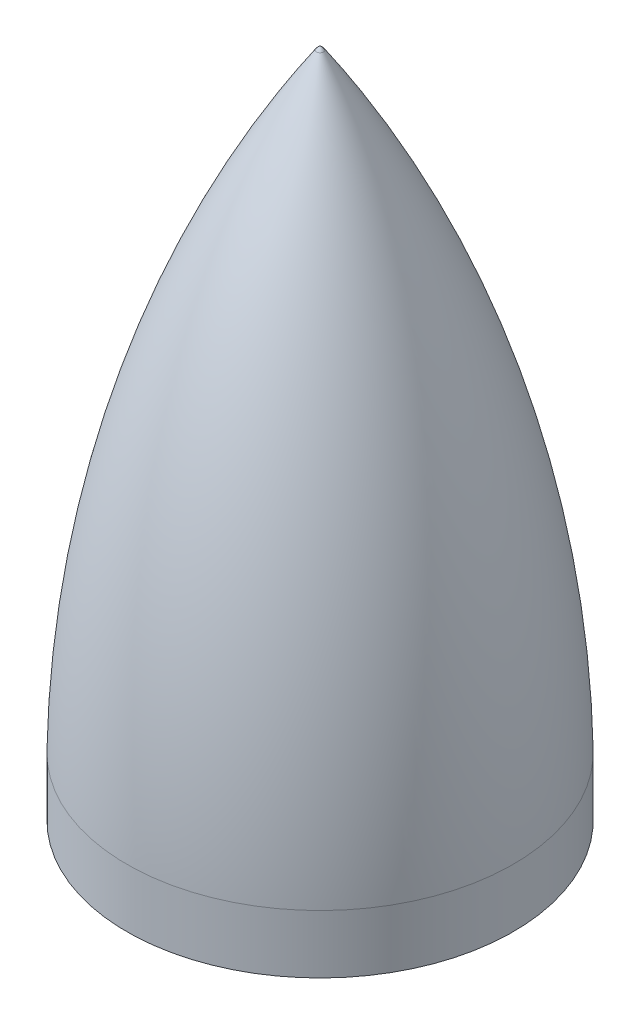
SolidWorks part; units mm, degrees
ref_plane "Спереди" through (0, 0, 0) normal (0, 0, 1) x (1, 0, 0)
ref_plane "Сверху" through (0, 0, 0) normal (0, 1, 0) x (1, 0, 0)
ref_plane "Справа" through (0, 0, 0) normal (1, 0, 0) x (0, 0, -1)
other "Configuration Table"
sketch "Эскиз1" plane through (0, 0, 0) normal (0, 0, 1) x (1, 0, 0)
  line L0 (0, 0) -> (0, 76824.2673) construction
  line L1 (0, 0) -> (49.6, 0)
  line L2 (49.6, 0) -> (49.6, 15)
  line L3 (48.8, 4) -> (48.8, 14.9937)
  line L5 (0, 172.1926) -> (0, 171.1649)
  line L7 (0, 4) -> (48.8, 4)
  line L8 (0, 4) -> (0, 0)
  line L9 (48.8, 0.8) -> (48.8, 14.9937) construction
  line L10 (0, 0.8) -> (48.8, 0.8) construction
  arc A0 (0.8958, 171.3195) -> (49.6, 15) centre (-240.3636, 10.4037) cw
  arc A1 (0.2302, 170.8756) -> (0, 171.1649) centre (-1.6, 169.6549) ccw
  arc A2 (0.8958, 171.3195) -> (0, 172.1926) centre (-1.6, 169.6549) ccw
  arc A3 (0.2302, 170.8756) -> (48.8, 14.9937) centre (-240.3636, 10.4037) cw
  arc A4 (0.2302, 170.8756) -> (-0.4267, 171.5159) centre (-1.6, 169.6549) ccw construction
  dimension "D4" = 290
  dimension "D5" = 3
  dimension "D1" = 99.2
  dimension "D2" = 15
  dimension "D3" = 0.8
  dimension "D6" = 4
revolve "Повернуть2" add sketch "Эскиз1" angle 360 about L0
sketch "Эскиз2" plane through (0, 0, 0) normal (0, -1, 0) x (1, 0, 0)
  circle A0 centre (0, 0) radius 4.4
  dimension "D1" = 8.8
sketch "Эскиз3" plane through (0, 0, 0) normal (0, 0, 1) x (1, 0, 0)
  line L0 (0, 170.8756) -> (0, 0) construction
  line L1 (0.2302, 170.8756) -> (-0.2302, 170.8756) construction
  line L2 (0, 74) -> (6, 74)
  line L3 (6, 74) -> (6, 4)
  line L5 (6, 4) -> (0, 4)
  line L6 (48.8, 4) -> (-48.8, 4) construction
  line L7 (0, 4) -> (0, 74)
  point P7 (0, 6.3673)
  dimension "D1" = 70
  dimension "D2" = 12
revolve "Повернуть6" add sketch "Эскиз3" angle 360 about L0
extrude "Вырез-Вытянуть1" cut sketch "Эскиз2" against normal blind 70
sketch "Эскиз4" plane through (0, 0, 0) normal (0, -1, 0) x (1, 0, 0)
  line L0 (0, 0) -> (0, 49.6) construction
  line L1 (5, 48.5432) -> (5, 4.899)
  line L2 (-5, 48.5432) -> (-5, 4.899)
  line L3 (48.5432, 5) -> (4.899, 5)
  line L4 (48.5432, -5) -> (4.899, -5)
  line L5 (0, 0) -> (49.6, 0) construction
  line L6 (5, -48.5432) -> (5, -4.899)
  line L7 (-5, -48.5432) -> (-5, -4.899)
  line L8 (0, 0) -> (0, -49.6) construction
  line L9 (-48.5432, -5) -> (-4.899, -5)
  line L10 (-48.5432, 5) -> (-4.899, 5)
  line L11 (0, 0) -> (-49.6, 0) construction
  arc A0 (-4.899, -5) -> (-5, -4.899) centre (0, 0) ccw
  circle A1 centre (0, 0) radius 49.6 construction
  arc A3 (5, -4.899) -> (4.899, -5) centre (0, 0) ccw
  arc A4 (4.899, 5) -> (5, 4.899) centre (0, 0) ccw
  arc A5 (-5, 4.899) -> (-4.899, 5) centre (0, 0) ccw
  circle A8 centre (0, 0) radius 48.8
  point P29 (0, 0)
  dimension "D1" = 14
  dimension "D2" = 10
  dimension "D3" = 5
  dimension "D4" = 4
extrude "Вырез-Вытянуть2" cut sketch "Эскиз4" against normal blind 10 contours L2 A8 L10 A5 | L9 A8 L7 A0 | L6 A8 L4 A3 | L3 A8 L1 A4 region at (22.9077, 0, 22.9077) region at (-22.9077, 0, 22.9077) region at (22.9077, 0, -22.9077) region at (-22.9077, 0, -22.9077)
fillet "Скругление2" radius 5 8 edges at (5, 2, 48.5432) (-5, 2, 48.5432) (48.5432, 2, -5) (48.5432, 2, 5) (-5, 2, -48.5432) (5, 2, -48.5432) (-48.5432, 2, -5) (-48.5432, 2, 5)
fillet "Скругление3" radius 2 4 edges at (5, 2, -5) (5, 2, 5) (-5, 2, -5) (-5, 2, 5)
